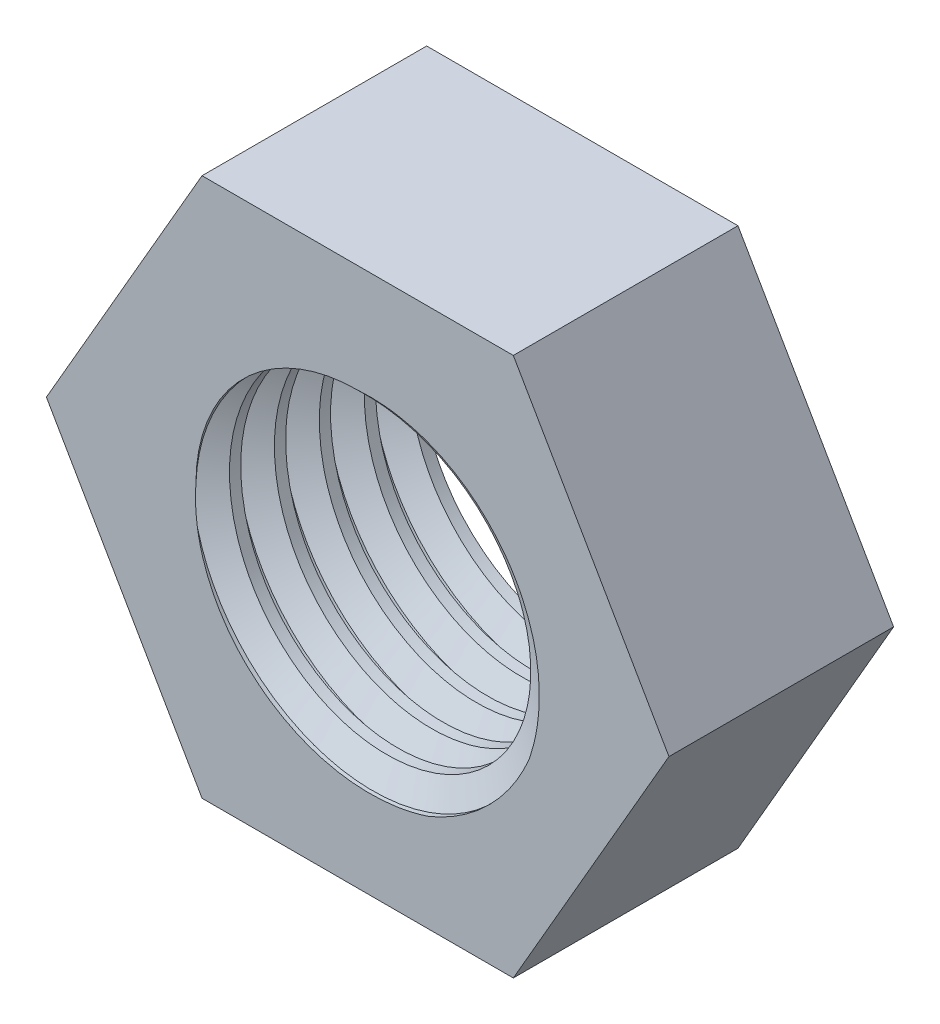
SolidWorks part; units mm, degrees
ref_plane "Top Plane" through (0, 0, 0) normal (0, 0, 1) x (1, 0, 0)
ref_plane "Front Plane" through (0, 0, 0) normal (0, 1, 0) x (1, 0, 0)
ref_plane "Right Plane" through (0, 0, 0) normal (1, 0, 0) x (0, 0, -1)
ref_plane "Top" through (0, 0, 0) normal (0, 0, 1) x (1, 0, 0)
ref_plane "Front" through (0, 0, 0) normal (0, 1, 0) x (1, 0, 0)
ref_plane "Right" through (0, 0, 0) normal (1, 0, 0) x (0, 0, -1)
ref_axis "X Axis" through (88.99, 0, 0) along (-1, 0, 0)
ref_axis "Y Axis" through (0, -55, 0) along (0, 1, 0)
ref_axis "Z Axis" through (0, 0, 55) along (0, 0, -1)
sketch "Sketch1" plane through (0, 0, 0) normal (0, 0, 1) x (1, 0, 0)
  line L1 (-3.4641, 6) -> (-6.9282, 0)
  line L2 (-6.9282, 0) -> (-3.4641, -6)
  line L3 (-3.4641, -6) -> (3.4641, -6)
  line L4 (3.4641, -6) -> (6.9282, 0)
  line L5 (6.9282, 0) -> (3.4641, 6)
  line L6 (3.4641, 6) -> (-3.4641, 6)
  circle A0 centre (0, 0) radius 6 construction
  dimension "D1" = 12
extrude "Boss-Extrude1" add sketch "Sketch1" along normal blind 5
sketch "Sketch2" plane through (0, 0, 5) normal (0, 0, 1) x (1, 0, 0)
  circle A0 centre (0, 0) radius 3.6
  dimension "D1" = 7.2
extrude "Cut-Extrude1" cut sketch "Sketch2" against normal through all
thread "Thread1" pitch 1 method cut trim with start face yes trim with end face yes profile "Thread Profile1" start angle 0, offset 1, length 0, pitch 1, diameter 7.2
ref_plane "Plane1" through (-3.6, 0, 6) normal (0, -1, 0) x (-1, 0, 0)
sketch "Thread Profile1" plane through (-3.6, 0, 6) normal (0, -1, 0) x (-1, 0, 0)
  line L0 (0, 0) -> (0, 1) construction
  line L1 (0, 0) -> (0.5413, 0.3125)
  line L2 (0.5413, 0.3125) -> (0.5413, 0.4375)
  line L3 (0.5413, 0.4375) -> (0, 0.75)
  line L4 (0.5413, 0.375) -> (0, 0.375) construction
  line L11 (0, 0) -> (0, 0.75)
  point P2 (0, 0)
  dimension "Pitch" = 1
  dimension "Profile_Angle" = 60
  dimension "Profile_Land" = 0.125
  dimension "Profile_Height" = 0.5413
